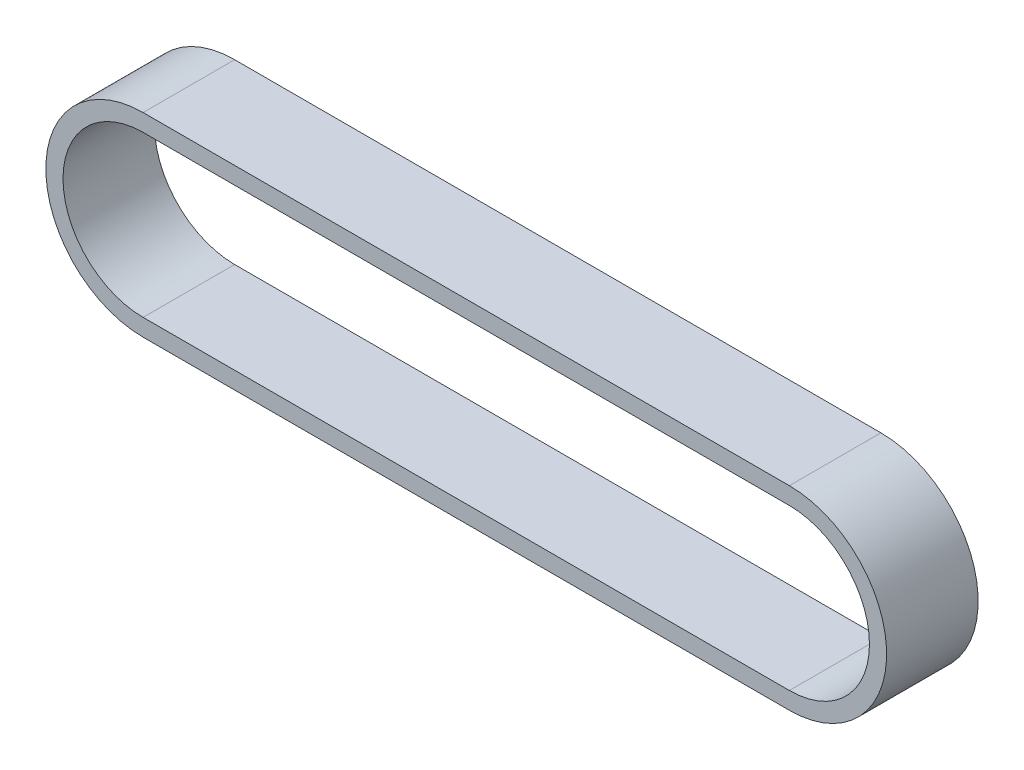
SolidWorks part; units mm, degrees
material "PF"
ref_plane "Piano frontale" through (0, 0, 0) normal (0, 0, 1) x (1, 0, 0)
ref_plane "Piano superiore" through (0, 0, 0) normal (0, 1, 0) x (1, 0, 0)
ref_plane "Piano destro" through (0, 0, 0) normal (1, 0, 0) x (0, 0, -1)
sketch "Schizzo1" plane through (0, 0, 0) normal (0, 0, 1) x (1, 0, 0)
  line L0 (0, 0) -> (-45.1774, 0) construction
  line L1 (0, -5.6) -> (-45.1774, -5.6)
  line L2 (0, 5.6) -> (-45.1774, 5.6)
  line L3 (0, 0) -> (-45.1774, 0) construction
  line L4 (0, -6.8) -> (-45.1774, -6.8)
  line L5 (0, 6.8) -> (-45.1774, 6.8)
  arc A0 (0, -5.6) -> (0, 5.6) centre (0, 0) ccw
  arc A1 (-45.1774, 5.6) -> (-45.1774, -5.6) centre (-45.1774, 0) ccw
  arc A2 (0, -6.8) -> (0, 6.8) centre (0, 0) ccw
  arc A3 (-45.1774, 6.8) -> (-45.1774, -6.8) centre (-45.1774, 0) ccw
  point P3 (-22.5887, 0)
  point P8 (-22.5887, 0)
  line B0 (0, 0) -> (-45.1774, 0) construction
  dimension "D2" = 5.6
  dimension "D1" = 1.2
sketch_block_instance "puleggia piccola-1"
sketch_block "puleggia piccola"
extrude "Estrusione-Estrusione2" add sketch "Schizzo1" along normal blind 6.4 contours L5 A3 L4 A2 A1 L2 A0 L1 region at (-22.5887, -6.1967, 0)
